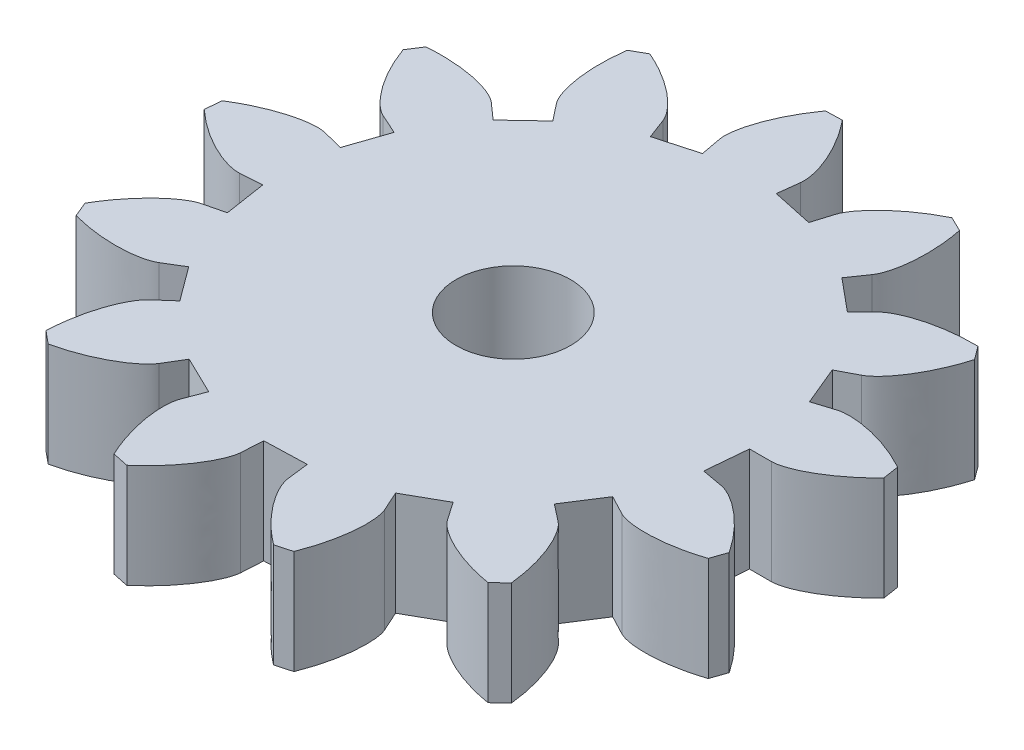
SolidWorks part; units mm, degrees
ref_plane "Front Plane" through (0, 0, 0) normal (0, 0, 1) x (1, 0, 0)
ref_plane "Top Plane" through (0, 0, 0) normal (0, 1, 0) x (1, 0, 0)
ref_plane "Right Plane" through (0, 0, 0) normal (1, 0, 0) x (0, 0, -1)
sketch "Sketch1" plane through (0, 0, 0) normal (0, 1, 0) x (1, 0, 0)
  circle A0 centre (0, 0) radius 8.2743 construction
  circle A1 centre (0, 0) radius 8.2743
sketch "Sketch2" plane through (0, 0, 0) normal (0, 1, 0) x (1, 0, 0)
  line L0 (6.8098, 0) -> (7.4374, 0)
  line L1 (7.4374, 0) -> (7.4435, 0.0002)
  line L2 (7.4435, 0.0002) -> (7.455, 0.0009)
  line L3 (7.455, 0.0009) -> (7.4719, 0.0023)
  line L4 (7.4719, 0.0023) -> (7.494, 0.0048)
  line L5 (7.494, 0.0048) -> (7.5213, 0.0086)
  line L6 (7.5213, 0.0086) -> (7.5538, 0.0141)
  line L7 (7.5538, 0.0141) -> (7.5915, 0.0214)
  line L8 (7.5915, 0.0214) -> (7.6341, 0.0309)
  line L9 (7.6341, 0.0309) -> (7.6817, 0.0428)
  line L10 (7.6817, 0.0428) -> (7.7341, 0.0575)
  line L11 (7.7341, 0.0575) -> (7.7912, 0.0751)
  line L12 (7.7912, 0.0751) -> (7.8529, 0.096)
  line L13 (7.8529, 0.096) -> (7.9191, 0.1204)
  line L14 (7.9191, 0.1204) -> (7.9895, 0.1486)
  line L15 (7.9895, 0.1486) -> (8.0641, 0.1807)
  line L16 (8.0641, 0.1807) -> (8.1427, 0.2171)
  line L17 (8.1427, 0.2171) -> (8.225, 0.258)
  line L18 (8.225, 0.258) -> (8.311, 0.3036)
  line L19 (8.311, 0.3036) -> (8.4004, 0.3541)
  line L20 (8.4004, 0.3541) -> (8.493, 0.4097)
  line L21 (8.493, 0.4097) -> (8.5886, 0.4707)
  line L22 (8.5886, 0.4707) -> (8.6869, 0.5373)
  line L23 (8.6869, 0.5373) -> (8.7878, 0.6095)
  line L24 (8.7878, 0.6095) -> (8.891, 0.6877)
  line L25 (8.891, 0.6877) -> (8.9962, 0.772)
  line L26 (8.9962, 0.772) -> (9.1033, 0.8626)
  line L27 (9.1033, 0.8626) -> (9.2118, 0.9596)
  line L28 (9.2118, 0.9596) -> (9.3216, 1.0631)
  line L29 (9.3216, 1.0631) -> (9.4324, 1.1733)
  line L30 (9.4324, 1.1733) -> (9.4602, 1.2019)
  line L31 (9.4602, 1.2019) -> (9.4672, 1.2092)
  line L32 (9.4672, 1.2092) -> (9.4689, 1.211)
  line L33 (9.4689, 1.211) -> (9.4692, 1.2112)
  line L34 (9.4692, 1.2112) -> (9.4693, 1.2114)
  line L35 (9.4693, 1.2114) -> (9.3971, 1.6821)
  line L36 (9.3971, 1.6821) -> (9.3969, 1.6823)
  line L37 (9.3969, 1.6823) -> (9.3966, 1.6825)
  line L38 (9.3966, 1.6825) -> (9.3944, 1.6837)
  line L39 (9.3944, 1.6837) -> (9.3856, 1.6885)
  line L40 (9.3856, 1.6885) -> (9.3505, 1.7074)
  line L41 (9.3505, 1.7074) -> (9.2118, 1.7794)
  line L42 (9.2118, 1.7794) -> (9.076, 1.8452)
  line L43 (9.076, 1.8452) -> (8.9434, 1.9052)
  line L44 (8.9434, 1.9052) -> (8.8141, 1.9595)
  line L45 (8.8141, 1.9595) -> (8.6884, 2.0084)
  line L46 (8.6884, 2.0084) -> (8.5666, 2.0521)
  line L47 (8.5666, 2.0521) -> (8.4487, 2.0908)
  line L48 (8.4487, 2.0908) -> (8.3349, 2.1248)
  line L49 (8.3349, 2.1248) -> (8.2254, 2.1544)
  line L50 (8.2254, 2.1544) -> (8.1204, 2.1797)
  line L51 (8.1204, 2.1797) -> (8.02, 2.2011)
  line L52 (8.02, 2.2011) -> (7.9243, 2.2189)
  line L53 (7.9243, 2.2189) -> (7.8335, 2.2332)
  line L54 (7.8335, 2.2332) -> (7.7476, 2.2443)
  line L55 (7.7476, 2.2443) -> (7.6668, 2.2527)
  line L56 (7.6668, 2.2527) -> (7.5912, 2.2584)
  line L57 (7.5912, 2.2584) -> (7.5207, 2.2618)
  line L58 (7.5207, 2.2618) -> (7.4556, 2.2633)
  line L59 (7.4556, 2.2633) -> (7.3958, 2.263)
  line L60 (7.3958, 2.263) -> (7.3415, 2.2613)
  line L61 (7.3415, 2.2613) -> (7.2925, 2.2584)
  line L62 (7.2925, 2.2584) -> (7.2489, 2.2547)
  line L63 (7.2489, 2.2547) -> (7.2109, 2.2504)
  line L64 (7.2109, 2.2504) -> (7.1782, 2.2458)
  line L65 (7.1782, 2.2458) -> (7.151, 2.2413)
  line L66 (7.151, 2.2413) -> (7.1291, 2.237)
  line L67 (7.1291, 2.237) -> (7.1126, 2.2334)
  line L68 (7.1126, 2.2334) -> (7.1015, 2.2306)
  line L69 (7.1015, 2.2306) -> (7.0955, 2.2289)
  line L70 (7.0955, 2.2289) -> (6.4968, 2.0408)
  line L71 (6.4968, 2.0408) -> (6.0298, 3.1647)
  line L72 (6.0298, 3.1647) -> (6.5855, 3.4563)
  line L73 (6.5855, 3.4563) -> (6.5908, 3.4594)
  line L74 (6.5908, 3.4594) -> (6.6007, 3.4653)
  line L75 (6.6007, 3.4653) -> (6.6149, 3.4744)
  line L76 (6.6149, 3.4744) -> (6.6333, 3.4869)
  line L77 (6.6333, 3.4869) -> (6.6558, 3.503)
  line L78 (6.6558, 3.503) -> (6.6821, 3.5229)
  line L79 (6.6821, 3.5229) -> (6.712, 3.5469)
  line L80 (6.712, 3.5469) -> (6.7453, 3.5751)
  line L81 (6.7453, 3.5751) -> (6.7819, 3.6078)
  line L82 (6.7819, 3.6078) -> (6.8215, 3.6451)
  line L83 (6.8215, 3.6451) -> (6.8639, 3.6873)
  line L84 (6.8639, 3.6873) -> (6.9088, 3.7345)
  line L85 (6.9088, 3.7345) -> (6.956, 3.7868)
  line L86 (6.956, 3.7868) -> (7.0053, 3.8445)
  line L87 (7.0053, 3.8445) -> (7.0564, 3.9076)
  line L88 (7.0564, 3.9076) -> (7.1091, 3.9763)
  line L89 (7.1091, 3.9763) -> (7.163, 4.0508)
  line L90 (7.163, 4.0508) -> (7.218, 4.1311)
  line L91 (7.218, 4.1311) -> (7.2736, 4.2174)
  line L92 (7.2736, 4.2174) -> (7.3298, 4.3097)
  line L93 (7.3298, 4.3097) -> (7.3861, 4.4081)
  line L94 (7.3861, 4.4081) -> (7.4422, 4.5127)
  line L95 (7.4422, 4.5127) -> (7.498, 4.6236)
  line L96 (7.498, 4.6236) -> (7.553, 4.7408)
  line L97 (7.553, 4.7408) -> (7.607, 4.8644)
  line L98 (7.607, 4.8644) -> (7.6597, 4.9943)
  line L99 (7.6597, 4.9943) -> (7.7107, 5.1306)
  line L100 (7.7107, 5.1306) -> (7.7598, 5.2733)
  line L101 (7.7598, 5.2733) -> (7.8067, 5.4224)
  line L102 (7.8067, 5.4224) -> (7.8181, 5.4607)
  line L103 (7.8181, 5.4607) -> (7.8209, 5.4703)
  line L104 (7.8209, 5.4703) -> (7.8216, 5.4727)
  line L105 (7.8216, 5.4727) -> (7.8217, 5.473)
  line L106 (7.8217, 5.473) -> (7.8216, 5.4732)
  line L107 (7.8216, 5.4732) -> (7.539, 5.8565)
  line L108 (7.539, 5.8565) -> (7.5387, 5.8566)
  line L109 (7.5387, 5.8566) -> (7.5384, 5.8566)
  line L110 (7.5384, 5.8566) -> (7.5359, 5.8566)
  line L111 (7.5359, 5.8566) -> (7.5259, 5.8568)
  line L112 (7.5259, 5.8568) -> (7.486, 5.8572)
  line L113 (7.486, 5.8572) -> (7.3297, 5.8565)
  line L114 (7.3297, 5.8565) -> (7.1789, 5.8517)
  line L115 (7.1789, 5.8517) -> (7.0336, 5.8432)
  line L116 (7.0336, 5.8432) -> (6.8939, 5.8312)
  line L117 (6.8939, 5.8312) -> (6.7599, 5.8161)
  line L118 (6.7599, 5.8161) -> (6.6317, 5.7981)
  line L119 (6.6317, 5.7981) -> (6.5093, 5.7776)
  line L120 (6.5093, 5.7776) -> (6.3927, 5.7549)
  line L121 (6.3927, 5.7549) -> (6.282, 5.7302)
  line L122 (6.282, 5.7302) -> (6.1773, 5.7038)
  line L123 (6.1773, 5.7038) -> (6.0784, 5.6761)
  line L124 (6.0784, 5.6761) -> (5.9855, 5.6473)
  line L125 (5.9855, 5.6473) -> (5.8984, 5.6178)
  line L126 (5.8984, 5.6178) -> (5.8172, 5.5878)
  line L127 (5.8172, 5.5878) -> (5.7418, 5.5576)
  line L128 (5.7418, 5.5576) -> (5.6721, 5.5275)
  line L129 (5.6721, 5.5275) -> (5.6082, 5.4978)
  line L130 (5.6082, 5.4978) -> (5.5498, 5.4688)
  line L131 (5.5498, 5.4688) -> (5.497, 5.4408)
  line L132 (5.497, 5.4408) -> (5.4497, 5.414)
  line L133 (5.4497, 5.414) -> (5.4076, 5.3887)
  line L134 (5.4076, 5.3887) -> (5.3708, 5.3652)
  line L135 (5.3708, 5.3652) -> (5.3391, 5.3437)
  line L136 (5.3391, 5.3437) -> (5.3123, 5.3245)
  line L137 (5.3123, 5.3245) -> (5.2903, 5.3078)
  line L138 (5.2903, 5.3078) -> (5.2729, 5.2939)
  line L139 (5.2729, 5.2939) -> (5.26, 5.283)
  line L140 (5.26, 5.283) -> (5.2514, 5.2753)
  line L141 (5.2514, 5.2753) -> (5.247, 5.2711)
  line L142 (5.247, 5.2711) -> (4.8042, 4.8263)
  line L143 (4.8042, 4.8263) -> (3.8684, 5.6043)
  line L144 (3.8684, 5.6043) -> (4.2249, 6.1208)
  line L145 (4.2249, 6.1208) -> (4.2282, 6.126)
  line L146 (4.2282, 6.126) -> (4.2342, 6.1359)
  line L147 (4.2342, 6.1359) -> (4.2426, 6.1505)
  line L148 (4.2426, 6.1505) -> (4.2531, 6.1702)
  line L149 (4.2531, 6.1702) -> (4.2655, 6.1948)
  line L150 (4.2655, 6.1948) -> (4.2795, 6.2247)
  line L151 (4.2795, 6.2247) -> (4.2948, 6.2598)
  line L152 (4.2948, 6.2598) -> (4.3112, 6.3003)
  line L153 (4.3112, 6.3003) -> (4.3284, 6.3462)
  line L154 (4.3284, 6.3462) -> (4.3462, 6.3977)
  line L155 (4.3462, 6.3977) -> (4.3641, 6.4547)
  line L156 (4.3641, 6.4547) -> (4.3819, 6.5174)
  line L157 (4.3819, 6.5174) -> (4.3994, 6.5857)
  line L158 (4.3994, 6.5857) -> (4.4163, 6.6596)
  line L159 (4.4163, 6.6596) -> (4.4322, 6.7393)
  line L160 (4.4322, 6.7393) -> (4.4469, 6.8246)
  line L161 (4.4469, 6.8246) -> (4.46, 6.9156)
  line L162 (4.46, 6.9156) -> (4.4714, 7.0123)
  line L163 (4.4714, 7.0123) -> (4.4806, 7.1145)
  line L164 (4.4806, 7.1145) -> (4.4874, 7.2223)
  line L165 (4.4874, 7.2223) -> (4.4915, 7.3356)
  line L166 (4.4915, 7.3356) -> (4.4926, 7.4544)
  line L167 (4.4926, 7.4544) -> (4.4904, 7.5785)
  line L168 (4.4904, 7.5785) -> (4.4847, 7.7078)
  line L169 (4.4847, 7.7078) -> (4.4751, 7.8423)
  line L170 (4.4751, 7.8423) -> (4.4613, 7.9819)
  line L171 (4.4613, 7.9819) -> (4.4432, 8.1263)
  line L172 (4.4432, 8.1263) -> (4.4204, 8.2755)
  line L173 (4.4204, 8.2755) -> (4.3926, 8.4293)
  line L174 (4.3926, 8.4293) -> (4.3849, 8.4684)
  line L175 (4.3849, 8.4684) -> (4.3829, 8.4782)
  line L176 (4.3829, 8.4782) -> (4.3824, 8.4807)
  line L177 (4.3824, 8.4807) -> (4.3823, 8.481)
  line L178 (4.3823, 8.481) -> (4.3822, 8.4812)
  line L179 (4.3822, 8.4812) -> (3.9538, 8.6892)
  line L180 (3.9538, 8.6892) -> (3.9535, 8.6892)
  line L181 (3.9535, 8.6892) -> (3.9533, 8.689)
  line L182 (3.9533, 8.689) -> (3.951, 8.6879)
  line L183 (3.951, 8.6879) -> (3.9421, 8.6834)
  line L184 (3.9421, 8.6834) -> (3.9065, 8.6652)
  line L185 (3.9065, 8.6652) -> (3.7685, 8.5919)
  line L186 (3.7685, 8.5919) -> (3.6371, 8.5176)
  line L187 (3.6371, 8.5176) -> (3.5125, 8.4425)
  line L188 (3.5125, 8.4425) -> (3.3943, 8.367)
  line L189 (3.3943, 8.367) -> (3.2827, 8.2914)
  line L190 (3.2827, 8.2914) -> (3.1775, 8.2159)
  line L191 (3.1775, 8.2159) -> (3.0787, 8.1408)
  line L192 (3.0787, 8.1408) -> (2.986, 8.0665)
  line L193 (2.986, 8.0665) -> (2.8995, 7.9932)
  line L194 (2.8995, 7.9932) -> (2.819, 7.9212)
  line L195 (2.819, 7.9212) -> (2.7444, 7.8507)
  line L196 (2.7444, 7.8507) -> (2.6754, 7.782)
  line L197 (2.6754, 7.782) -> (2.6121, 7.7154)
  line L198 (2.6121, 7.7154) -> (2.5541, 7.6511)
  line L199 (2.5541, 7.6511) -> (2.5013, 7.5893)
  line L200 (2.5013, 7.5893) -> (2.4537, 7.5303)
  line L201 (2.4537, 7.5303) -> (2.4108, 7.4743)
  line L202 (2.4108, 7.4743) -> (2.3726, 7.4215)
  line L203 (2.3726, 7.4215) -> (2.3389, 7.3722)
  line L204 (2.3389, 7.3722) -> (2.3094, 7.3265)
  line L205 (2.3094, 7.3265) -> (2.284, 7.2845)
  line L206 (2.284, 7.2845) -> (2.2623, 7.2466)
  line L207 (2.2623, 7.2466) -> (2.2442, 7.2128)
  line L208 (2.2442, 7.2128) -> (2.2294, 7.1833)
  line L209 (2.2294, 7.1833) -> (2.2177, 7.1583)
  line L210 (2.2177, 7.1583) -> (2.2088, 7.1379)
  line L211 (2.2088, 7.1379) -> (2.2024, 7.1223)
  line L212 (2.2024, 7.1223) -> (2.1984, 7.1115)
  line L213 (2.1984, 7.1115) -> (2.1964, 7.1057)
  line L214 (2.1964, 7.1057) -> (2.011, 6.5061)
  line L215 (2.011, 6.5061) -> (0.8208, 6.7601)
  line L216 (0.8208, 6.7601) -> (0.8965, 7.3831)
  line L217 (0.8965, 7.3831) -> (0.897, 7.3893)
  line L218 (0.897, 7.3893) -> (0.8977, 7.4008)
  line L219 (0.8977, 7.4008) -> (0.8983, 7.4177)
  line L220 (0.8983, 7.4177) -> (0.8985, 7.4399)
  line L221 (0.8985, 7.4399) -> (0.898, 7.4675)
  line L222 (0.898, 7.4675) -> (0.8965, 7.5005)
  line L223 (0.8965, 7.5005) -> (0.8938, 7.5387)
  line L224 (0.8938, 7.5387) -> (0.8895, 7.5822)
  line L225 (0.8895, 7.5822) -> (0.8834, 7.6309)
  line L226 (0.8834, 7.6309) -> (0.8752, 7.6846)
  line L227 (0.8752, 7.6846) -> (0.8645, 7.7435)
  line L228 (0.8645, 7.7435) -> (0.8512, 7.8072)
  line L229 (0.8512, 7.8072) -> (0.835, 7.8758)
  line L230 (0.835, 7.8758) -> (0.8156, 7.9492)
  line L231 (0.8156, 7.9492) -> (0.7926, 8.0271)
  line L232 (0.7926, 8.0271) -> (0.766, 8.1095)
  line L233 (0.766, 8.1095) -> (0.7353, 8.1962)
  line L234 (0.7353, 8.1962) -> (0.7004, 8.287)
  line L235 (0.7004, 8.287) -> (0.6611, 8.3818)
  line L236 (0.6611, 8.3818) -> (0.617, 8.4804)
  line L237 (0.617, 8.4804) -> (0.568, 8.5827)
  line L238 (0.568, 8.5827) -> (0.5138, 8.6883)
  line L239 (0.5138, 8.6883) -> (0.4542, 8.7972)
  line L240 (0.4542, 8.7972) -> (0.389, 8.9091)
  line L241 (0.389, 8.9091) -> (0.318, 9.0237)
  line L242 (0.318, 9.0237) -> (0.241, 9.1409)
  line L243 (0.241, 9.1409) -> (0.1578, 9.2603)
  line L244 (0.1578, 9.2603) -> (0.0682, 9.3818)
  line L245 (0.0682, 9.3818) -> (-0.0278, 9.5051)
  line L246 (-0.0278, 9.5051) -> (-0.0529, 9.5361)
  line L247 (-0.0529, 9.5361) -> (-0.0592, 9.5439)
  line L248 (-0.0592, 9.5439) -> (-0.0608, 9.5459)
  line L249 (-0.0608, 9.5459) -> (-0.061, 9.5461)
  line L250 (-0.061, 9.5461) -> (-0.0612, 9.5462)
  line L251 (-0.0612, 9.5462) -> (-0.5372, 9.5313)
  line L252 (-0.5372, 9.5313) -> (-0.5374, 9.5312)
  line L253 (-0.5374, 9.5312) -> (-0.5375, 9.5309)
  line L254 (-0.5375, 9.5309) -> (-0.539, 9.5289)
  line L255 (-0.539, 9.5289) -> (-0.5448, 9.5207)
  line L256 (-0.5448, 9.5207) -> (-0.5679, 9.4881)
  line L257 (-0.5679, 9.4881) -> (-0.656, 9.3591)
  line L258 (-0.656, 9.3591) -> (-0.7378, 9.2322)
  line L259 (-0.7378, 9.2322) -> (-0.8133, 9.1078)
  line L260 (-0.8133, 9.1078) -> (-0.8828, 8.986)
  line L261 (-0.8828, 8.986) -> (-0.9465, 8.8672)
  line L262 (-0.9465, 8.8672) -> (-1.0046, 8.7515)
  line L263 (-1.0046, 8.7515) -> (-1.0572, 8.6391)
  line L264 (-1.0572, 8.6391) -> (-1.1047, 8.5302)
  line L265 (-1.1047, 8.5302) -> (-1.1472, 8.4251)
  line L266 (-1.1472, 8.4251) -> (-1.185, 8.3239)
  line L267 (-1.185, 8.3239) -> (-1.2184, 8.2268)
  line L268 (-1.2184, 8.2268) -> (-1.2475, 8.134)
  line L269 (-1.2475, 8.134) -> (-1.2727, 8.0455)
  line L270 (-1.2727, 8.0455) -> (-1.2941, 7.9616)
  line L271 (-1.2941, 7.9616) -> (-1.3121, 7.8824)
  line L272 (-1.3121, 7.8824) -> (-1.3269, 7.808)
  line L273 (-1.3269, 7.808) -> (-1.3388, 7.7385)
  line L274 (-1.3388, 7.7385) -> (-1.3481, 7.6741)
  line L275 (-1.3481, 7.6741) -> (-1.355, 7.6147)
  line L276 (-1.355, 7.6147) -> (-1.3599, 7.5605)
  line L277 (-1.3599, 7.5605) -> (-1.3629, 7.5115)
  line L278 (-1.3629, 7.5115) -> (-1.3645, 7.4679)
  line L279 (-1.3645, 7.4679) -> (-1.3648, 7.4295)
  line L280 (-1.3648, 7.4295) -> (-1.3642, 7.3966)
  line L281 (-1.3642, 7.3966) -> (-1.363, 7.369)
  line L282 (-1.363, 7.369) -> (-1.3614, 7.3468)
  line L283 (-1.3614, 7.3468) -> (-1.3597, 7.33)
  line L284 (-1.3597, 7.33) -> (-1.3583, 7.3186)
  line L285 (-1.3583, 7.3186) -> (-1.3574, 7.3125)
  line L286 (-1.3574, 7.3125) -> (-1.2429, 6.6954)
  line L287 (-1.2429, 6.6954) -> (-2.4148, 6.3673)
  line L288 (-2.4148, 6.3673) -> (-2.6373, 6.9541)
  line L289 (-2.6373, 6.9541) -> (-2.6397, 6.9598)
  line L290 (-2.6397, 6.9598) -> (-2.6444, 6.9703)
  line L291 (-2.6444, 6.9703) -> (-2.6517, 6.9855)
  line L292 (-2.6517, 6.9855) -> (-2.6619, 7.0053)
  line L293 (-2.6619, 7.0053) -> (-2.6752, 7.0295)
  line L294 (-2.6752, 7.0295) -> (-2.6918, 7.058)
  line L295 (-2.6918, 7.058) -> (-2.712, 7.0906)
  line L296 (-2.712, 7.0906) -> (-2.736, 7.1271)
  line L297 (-2.736, 7.1271) -> (-2.764, 7.1673)
  line L298 (-2.764, 7.1673) -> (-2.7963, 7.2111)
  line L299 (-2.7963, 7.2111) -> (-2.8331, 7.2583)
  line L300 (-2.8331, 7.2583) -> (-2.8745, 7.3086)
  line L301 (-2.8745, 7.3086) -> (-2.9207, 7.3618)
  line L302 (-2.9207, 7.3618) -> (-2.972, 7.4176)
  line L303 (-2.972, 7.4176) -> (-3.0285, 7.476)
  line L304 (-3.0285, 7.476) -> (-3.0904, 7.5365)
  line L305 (-3.0904, 7.5365) -> (-3.1578, 7.5991)
  line L306 (-3.1578, 7.5991) -> (-3.2309, 7.6633)
  line L307 (-3.2309, 7.6633) -> (-3.3099, 7.729)
  line L308 (-3.3099, 7.729) -> (-3.3947, 7.7958)
  line L309 (-3.3947, 7.7958) -> (-3.4857, 7.8635)
  line L310 (-3.4857, 7.8635) -> (-3.5828, 7.9319)
  line L311 (-3.5828, 7.9319) -> (-3.6861, 8.0006)
  line L312 (-3.6861, 8.0006) -> (-3.7958, 8.0694)
  line L313 (-3.7958, 8.0694) -> (-3.912, 8.1379)
  line L314 (-3.912, 8.1379) -> (-4.0346, 8.2058)
  line L315 (-4.0346, 8.2058) -> (-4.1638, 8.2729)
  line L316 (-4.1638, 8.2729) -> (-4.2995, 8.3389)
  line L317 (-4.2995, 8.3389) -> (-4.4419, 8.4034)
  line L318 (-4.4419, 8.4034) -> (-4.4785, 8.4193)
  line L319 (-4.4785, 8.4193) -> (-4.4877, 8.4232)
  line L320 (-4.4877, 8.4232) -> (-4.49, 8.4242)
  line L321 (-4.49, 8.4242) -> (-4.4903, 8.4243)
  line L322 (-4.4903, 8.4243) -> (-4.4905, 8.4243)
  line L323 (-4.4905, 8.4243) -> (-4.9051, 8.1899)
  line L324 (-4.9051, 8.1899) -> (-4.9052, 8.1897)
  line L325 (-4.9052, 8.1897) -> (-4.9052, 8.1894)
  line L326 (-4.9052, 8.1894) -> (-4.9056, 8.1869)
  line L327 (-4.9056, 8.1869) -> (-4.9069, 8.177)
  line L328 (-4.9069, 8.177) -> (-4.9122, 8.1374)
  line L329 (-4.9122, 8.1374) -> (-4.9303, 7.9822)
  line L330 (-4.9303, 7.9822) -> (-4.9437, 7.8319)
  line L331 (-4.9437, 7.8319) -> (-4.9528, 7.6866)
  line L332 (-4.9528, 7.6866) -> (-4.9577, 7.5465)
  line L333 (-4.9577, 7.5465) -> (-4.9589, 7.4116)
  line L334 (-4.9589, 7.4116) -> (-4.9565, 7.2822)
  line L335 (-4.9565, 7.2822) -> (-4.9509, 7.1582)
  line L336 (-4.9509, 7.1582) -> (-4.9424, 7.0398)
  line L337 (-4.9424, 7.0398) -> (-4.9312, 6.9269)
  line L338 (-4.9312, 6.9269) -> (-4.9176, 6.8197)
  line L339 (-4.9176, 6.8197) -> (-4.902, 6.7183)
  line L340 (-4.902, 6.7183) -> (-4.8847, 6.6225)
  line L341 (-4.8847, 6.6225) -> (-4.8658, 6.5325)
  line L342 (-4.8658, 6.5325) -> (-4.8458, 6.4483)
  line L343 (-4.8458, 6.4483) -> (-4.825, 6.3698)
  line L344 (-4.825, 6.3698) -> (-4.8035, 6.297)
  line L345 (-4.8035, 6.297) -> (-4.7818, 6.23)
  line L346 (-4.7818, 6.23) -> (-4.76, 6.1686)
  line L347 (-4.76, 6.1686) -> (-4.7385, 6.1128)
  line L348 (-4.7385, 6.1128) -> (-4.7176, 6.0625)
  line L349 (-4.7176, 6.0625) -> (-4.6976, 6.0177)
  line L350 (-4.6976, 6.0177) -> (-4.6787, 5.9784)
  line L351 (-4.6787, 5.9784) -> (-4.6612, 5.9443)
  line L352 (-4.6612, 5.9443) -> (-4.6453, 5.9154)
  line L353 (-4.6453, 5.9154) -> (-4.6314, 5.8915)
  line L354 (-4.6314, 5.8915) -> (-4.6197, 5.8726)
  line L355 (-4.6197, 5.8726) -> (-4.6104, 5.8585)
  line L356 (-4.6104, 5.8585) -> (-4.6038, 5.849)
  line L357 (-4.6038, 5.849) -> (-4.6002, 5.8441)
  line L358 (-4.6002, 5.8441) -> (-4.212, 5.3509)
  line L359 (-4.212, 5.3509) -> (-5.0972, 4.5157)
  line L360 (-5.0972, 4.5157) -> (-5.567, 4.9319)
  line L361 (-5.567, 4.9319) -> (-5.5717, 4.9358)
  line L362 (-5.5717, 4.9358) -> (-5.5808, 4.9429)
  line L363 (-5.5808, 4.9429) -> (-5.5943, 4.953)
  line L364 (-5.5943, 4.953) -> (-5.6125, 4.9658)
  line L365 (-5.6125, 4.9658) -> (-5.6355, 4.9811)
  line L366 (-5.6355, 4.9811) -> (-5.6635, 4.9986)
  line L367 (-5.6635, 4.9986) -> (-5.6965, 5.0181)
  line L368 (-5.6965, 5.0181) -> (-5.7347, 5.0392)
  line L369 (-5.7347, 5.0392) -> (-5.7782, 5.0618)
  line L370 (-5.7782, 5.0618) -> (-5.8272, 5.0856)
  line L371 (-5.8272, 5.0856) -> (-5.8816, 5.1103)
  line L372 (-5.8816, 5.1103) -> (-5.9417, 5.1356)
  line L373 (-5.9417, 5.1356) -> (-6.0074, 5.1612)
  line L374 (-6.0074, 5.1612) -> (-6.0787, 5.1868)
  line L375 (-6.0787, 5.1868) -> (-6.1559, 5.2122)
  line L376 (-6.1559, 5.2122) -> (-6.2388, 5.2371)
  line L377 (-6.2388, 5.2371) -> (-6.3276, 5.2611)
  line L378 (-6.3276, 5.2611) -> (-6.4222, 5.284)
  line L379 (-6.4222, 5.284) -> (-6.5226, 5.3055)
  line L380 (-6.5226, 5.3055) -> (-6.6288, 5.3252)
  line L381 (-6.6288, 5.3252) -> (-6.7408, 5.3429)
  line L382 (-6.7408, 5.3429) -> (-6.8585, 5.3584)
  line L383 (-6.8585, 5.3584) -> (-6.982, 5.3712)
  line L384 (-6.982, 5.3712) -> (-7.1111, 5.381)
  line L385 (-7.1111, 5.381) -> (-7.2457, 5.3877)
  line L386 (-7.2457, 5.3877) -> (-7.3859, 5.3909)
  line L387 (-7.3859, 5.3909) -> (-7.5315, 5.3903)
  line L388 (-7.5315, 5.3903) -> (-7.6823, 5.3856)
  line L389 (-7.6823, 5.3856) -> (-7.8383, 5.3766)
  line L390 (-7.8383, 5.3766) -> (-7.8781, 5.3736)
  line L391 (-7.8781, 5.3736) -> (-7.8881, 5.3729)
  line L392 (-7.8881, 5.3729) -> (-7.8906, 5.3727)
  line L393 (-7.8906, 5.3727) -> (-7.8909, 5.3726)
  line L394 (-7.8909, 5.3726) -> (-7.8912, 5.3725)
  line L395 (-7.8912, 5.3725) -> (-8.1493, 4.9723)
  line L396 (-8.1493, 4.9723) -> (-8.1493, 4.9721)
  line L397 (-8.1493, 4.9721) -> (-8.1492, 4.9718)
  line L398 (-8.1492, 4.9718) -> (-8.1483, 4.9694)
  line L399 (-8.1483, 4.9694) -> (-8.1449, 4.96)
  line L400 (-8.1449, 4.96) -> (-8.1312, 4.9225)
  line L401 (-8.1312, 4.9225) -> (-8.0751, 4.7767)
  line L402 (-8.0751, 4.7767) -> (-8.0171, 4.6373)
  line L403 (-8.0171, 4.6373) -> (-7.9576, 4.5045)
  line L404 (-7.9576, 4.5045) -> (-7.8969, 4.3781)
  line L405 (-7.8969, 4.3781) -> (-7.8352, 4.2582)
  line L406 (-7.8352, 4.2582) -> (-7.773, 4.1447)
  line L407 (-7.773, 4.1447) -> (-7.7104, 4.0375)
  line L408 (-7.7104, 4.0375) -> (-7.6478, 3.9366)
  line L409 (-7.6478, 3.9366) -> (-7.5854, 3.8419)
  line L410 (-7.5854, 3.8419) -> (-7.5236, 3.7533)
  line L411 (-7.5236, 3.7533) -> (-7.4627, 3.6707)
  line L412 (-7.4627, 3.6707) -> (-7.4028, 3.5939)
  line L413 (-7.4028, 3.5939) -> (-7.3443, 3.523)
  line L414 (-7.3443, 3.523) -> (-7.2874, 3.4577)
  line L415 (-7.2874, 3.4577) -> (-7.2325, 3.3979)
  line L416 (-7.2325, 3.3979) -> (-7.1797, 3.3434)
  line L417 (-7.1797, 3.3434) -> (-7.1292, 3.2942)
  line L418 (-7.1292, 3.2942) -> (-7.0814, 3.2499)
  line L419 (-7.0814, 3.2499) -> (-7.0365, 3.2105)
  line L420 (-7.0365, 3.2105) -> (-6.9947, 3.1757)
  line L421 (-6.9947, 3.1757) -> (-6.9561, 3.1454)
  line L422 (-6.9561, 3.1454) -> (-6.9211, 3.1193)
  line L423 (-6.9211, 3.1193) -> (-6.8897, 3.0972)
  line L424 (-6.8897, 3.0972) -> (-6.8622, 3.079)
  line L425 (-6.8622, 3.079) -> (-6.8388, 3.0643)
  line L426 (-6.8388, 3.0643) -> (-6.8197, 3.0531)
  line L427 (-6.8197, 3.0531) -> (-6.8049, 3.0449)
  line L428 (-6.8049, 3.0449) -> (-6.7947, 3.0395)
  line L429 (-6.7947, 3.0395) -> (-6.7891, 3.0368)
  line L430 (-6.7891, 3.0368) -> (-6.2162, 2.7806)
  line L431 (-6.2162, 2.7806) -> (-6.6119, 1.6297)
  line L432 (-6.6119, 1.6297) -> (-7.2213, 1.7799)
  line L433 (-7.2213, 1.7799) -> (-7.2273, 1.7811)
  line L434 (-7.2273, 1.7811) -> (-7.2386, 1.7832)
  line L435 (-7.2386, 1.7832) -> (-7.2553, 1.7859)
  line L436 (-7.2553, 1.7859) -> (-7.2774, 1.7887)
  line L437 (-7.2774, 1.7887) -> (-7.3048, 1.7916)
  line L438 (-7.3048, 1.7916) -> (-7.3377, 1.7941)
  line L439 (-7.3377, 1.7941) -> (-7.376, 1.796)
  line L440 (-7.376, 1.796) -> (-7.4197, 1.797)
  line L441 (-7.4197, 1.797) -> (-7.4687, 1.7968)
  line L442 (-7.4687, 1.7968) -> (-7.5231, 1.7951)
  line L443 (-7.5231, 1.7951) -> (-7.5828, 1.7916)
  line L444 (-7.5828, 1.7916) -> (-7.6477, 1.7861)
  line L445 (-7.6477, 1.7861) -> (-7.7178, 1.7782)
  line L446 (-7.7178, 1.7782) -> (-7.7929, 1.7678)
  line L447 (-7.7929, 1.7678) -> (-7.873, 1.7544)
  line L448 (-7.873, 1.7544) -> (-7.958, 1.7379)
  line L449 (-7.958, 1.7379) -> (-8.0478, 1.7179)
  line L450 (-8.0478, 1.7179) -> (-8.1421, 1.6942)
  line L451 (-8.1421, 1.6942) -> (-8.241, 1.6666)
  line L452 (-8.241, 1.6666) -> (-8.3442, 1.6347)
  line L453 (-8.3442, 1.6347) -> (-8.4517, 1.5984)
  line L454 (-8.4517, 1.5984) -> (-8.5631, 1.5573)
  line L455 (-8.5631, 1.5573) -> (-8.6783, 1.5112)
  line L456 (-8.6783, 1.5112) -> (-8.7972, 1.46)
  line L457 (-8.7972, 1.46) -> (-8.9196, 1.4033)
  line L458 (-8.9196, 1.4033) -> (-9.0452, 1.341)
  line L459 (-9.0452, 1.341) -> (-9.1738, 1.2728)
  line L460 (-9.1738, 1.2728) -> (-9.3052, 1.1986)
  line L461 (-9.3052, 1.1986) -> (-9.4391, 1.1181)
  line L462 (-9.4391, 1.1181) -> (-9.473, 1.097)
  line L463 (-9.473, 1.097) -> (-9.4815, 1.0916)
  line L464 (-9.4815, 1.0916) -> (-9.4836, 1.0903)
  line L465 (-9.4836, 1.0903) -> (-9.4839, 1.0901)
  line L466 (-9.4839, 1.0901) -> (-9.484, 1.0899)
  line L467 (-9.484, 1.0899) -> (-9.5266, 0.6156)
  line L468 (-9.5266, 0.6156) -> (-9.5265, 0.6154)
  line L469 (-9.5265, 0.6154) -> (-9.5262, 0.6152)
  line L470 (-9.5262, 0.6152) -> (-9.5244, 0.6135)
  line L471 (-9.5244, 0.6135) -> (-9.517, 0.6067)
  line L472 (-9.517, 0.6067) -> (-9.4874, 0.5799)
  line L473 (-9.4874, 0.5799) -> (-9.3699, 0.4769)
  line L474 (-9.3699, 0.4769) -> (-9.2538, 0.3804)
  line L475 (-9.2538, 0.3804) -> (-9.1394, 0.2904)
  line L476 (-9.1394, 0.2904) -> (-9.0269, 0.2068)
  line L477 (-9.0269, 0.2068) -> (-8.9166, 0.1292)
  line L478 (-8.9166, 0.1292) -> (-8.8087, 0.0576)
  line L479 (-8.8087, 0.0576) -> (-8.7035, -0.0082)
  line L480 (-8.7035, -0.0082) -> (-8.6012, -0.0684)
  line L481 (-8.6012, -0.0684) -> (-8.502, -0.1233)
  line L482 (-8.502, -0.1233) -> (-8.4061, -0.1731)
  line L483 (-8.4061, -0.1731) -> (-8.3137, -0.2179)
  line L484 (-8.3137, -0.2179) -> (-8.225, -0.258)
  line L485 (-8.225, -0.258) -> (-8.1403, -0.2936)
  line L486 (-8.1403, -0.2936) -> (-8.0596, -0.325)
  line L487 (-8.0596, -0.325) -> (-7.9831, -0.3524)
  line L488 (-7.9831, -0.3524) -> (-7.911, -0.3761)
  line L489 (-7.911, -0.3761) -> (-7.8435, -0.3963)
  line L490 (-7.8435, -0.3963) -> (-7.7806, -0.4133)
  line L491 (-7.7806, -0.4133) -> (-7.7225, -0.4273)
  line L492 (-7.7225, -0.4273) -> (-7.6693, -0.4386)
  line L493 (-7.6693, -0.4386) -> (-7.6211, -0.4476)
  line L494 (-7.6211, -0.4476) -> (-7.5779, -0.4544)
  line L495 (-7.5779, -0.4544) -> (-7.5399, -0.4593)
  line L496 (-7.5399, -0.4593) -> (-7.5071, -0.4627)
  line L497 (-7.5071, -0.4627) -> (-7.4795, -0.4648)
  line L498 (-7.4795, -0.4648) -> (-7.4573, -0.4659)
  line L499 (-7.4573, -0.4659) -> (-7.4404, -0.4663)
  line L500 (-7.4404, -0.4663) -> (-7.4289, -0.4662)
  line L501 (-7.4289, -0.4662) -> (-7.4228, -0.4661)
  line L502 (-7.4228, -0.4661) -> (-6.7964, -0.4267)
  line L503 (-6.7964, -0.4267) -> (-6.6119, -1.6297)
  line L504 (-6.6119, -1.6297) -> (-7.2213, -1.7799)
  line L505 (-7.2213, -1.7799) -> (-7.2272, -1.7816)
  line L506 (-7.2272, -1.7816) -> (-7.2382, -1.785)
  line L507 (-7.2382, -1.785) -> (-7.2542, -1.7904)
  line L508 (-7.2542, -1.7904) -> (-7.2751, -1.7981)
  line L509 (-7.2751, -1.7981) -> (-7.3007, -1.8084)
  line L510 (-7.3007, -1.8084) -> (-7.331, -1.8214)
  line L511 (-7.331, -1.8214) -> (-7.3658, -1.8375)
  line L512 (-7.3658, -1.8375) -> (-7.4049, -1.857)
  line L513 (-7.4049, -1.857) -> (-7.4482, -1.8799)
  line L514 (-7.4482, -1.8799) -> (-7.4956, -1.9067)
  line L515 (-7.4956, -1.9067) -> (-7.5468, -1.9375)
  line L516 (-7.5468, -1.9375) -> (-7.6017, -1.9726)
  line L517 (-7.6017, -1.9726) -> (-7.6601, -2.0121)
  line L518 (-7.6601, -2.0121) -> (-7.7218, -2.0563)
  line L519 (-7.7218, -2.0563) -> (-7.7865, -2.1053)
  line L520 (-7.7865, -2.1053) -> (-7.8541, -2.1595)
  line L521 (-7.8541, -2.1595) -> (-7.9243, -2.2189)
  line L522 (-7.9243, -2.2189) -> (-7.9969, -2.2837)
  line L523 (-7.9969, -2.2837) -> (-8.0716, -2.3541)
  line L524 (-8.0716, -2.3541) -> (-8.1481, -2.4303)
  line L525 (-8.1481, -2.4303) -> (-8.2264, -2.5124)
  line L526 (-8.2264, -2.5124) -> (-8.3059, -2.6006)
  line L527 (-8.3059, -2.6006) -> (-8.3866, -2.6949)
  line L528 (-8.3866, -2.6949) -> (-8.4681, -2.7955)
  line L529 (-8.4681, -2.7955) -> (-8.5501, -2.9026)
  line L530 (-8.5501, -2.9026) -> (-8.6323, -3.0161)
  line L531 (-8.6323, -3.0161) -> (-8.7145, -3.1362)
  line L532 (-8.7145, -3.1362) -> (-8.7963, -3.263)
  line L533 (-8.7963, -3.263) -> (-8.8775, -3.3966)
  line L534 (-8.8775, -3.3966) -> (-8.8977, -3.431)
  line L535 (-8.8977, -3.431) -> (-8.9027, -3.4397)
  line L536 (-8.9027, -3.4397) -> (-8.904, -3.4418)
  line L537 (-8.904, -3.4418) -> (-8.9041, -3.4421)
  line L538 (-8.9041, -3.4421) -> (-8.9042, -3.4423)
  line L539 (-8.9042, -3.4423) -> (-8.7214, -3.8821)
  line L540 (-8.7214, -3.8821) -> (-8.7213, -3.8822)
  line L541 (-8.7213, -3.8822) -> (-8.7209, -3.8823)
  line L542 (-8.7209, -3.8823) -> (-8.7185, -3.883)
  line L543 (-8.7185, -3.883) -> (-8.7088, -3.8855)
  line L544 (-8.7088, -3.8855) -> (-8.6702, -3.8955)
  line L545 (-8.6702, -3.8955) -> (-8.5183, -3.9322)
  line L546 (-8.5183, -3.9322) -> (-8.3707, -3.9636)
  line L547 (-8.3707, -3.9636) -> (-8.2275, -3.9901)
  line L548 (-8.2275, -3.9901) -> (-8.089, -4.0119)
  line L549 (-8.089, -4.0119) -> (-7.9553, -4.0293)
  line L550 (-7.9553, -4.0293) -> (-7.8265, -4.0426)
  line L551 (-7.8265, -4.0426) -> (-7.7028, -4.052)
  line L552 (-7.7028, -4.052) -> (-7.5842, -4.0578)
  line L553 (-7.5842, -4.0578) -> (-7.4708, -4.0603)
  line L554 (-7.4708, -4.0603) -> (-7.3628, -4.0597)
  line L555 (-7.3628, -4.0597) -> (-7.2602, -4.0565)
  line L556 (-7.2602, -4.0565) -> (-7.163, -4.0508)
  line L557 (-7.163, -4.0508) -> (-7.0714, -4.0429)
  line L558 (-7.0714, -4.0429) -> (-6.9854, -4.0332)
  line L559 (-6.9854, -4.0332) -> (-6.9049, -4.022)
  line L560 (-6.9049, -4.022) -> (-6.8301, -4.0095)
  line L561 (-6.8301, -4.0095) -> (-6.7609, -3.9959)
  line L562 (-6.7609, -3.9959) -> (-6.6973, -3.9818)
  line L563 (-6.6973, -3.9818) -> (-6.6394, -3.9672)
  line L564 (-6.6394, -3.9672) -> (-6.587, -3.9525)
  line L565 (-6.587, -3.9525) -> (-6.5401, -3.938)
  line L566 (-6.5401, -3.938) -> (-6.4987, -3.924)
  line L567 (-6.4987, -3.924) -> (-6.4628, -3.9107)
  line L568 (-6.4628, -3.9107) -> (-6.4322, -3.8984)
  line L569 (-6.4322, -3.8984) -> (-6.4068, -3.8875)
  line L570 (-6.4068, -3.8875) -> (-6.3866, -3.8781)
  line L571 (-6.3866, -3.8781) -> (-6.3715, -3.8706)
  line L572 (-6.3715, -3.8706) -> (-6.3613, -3.8652)
  line L573 (-6.3613, -3.8652) -> (-6.3559, -3.8622)
  line L574 (-6.3559, -3.8622) -> (-5.8196, -3.5363)
  line L575 (-5.8196, -3.5363) -> (-5.0972, -4.5157)
  line L576 (-5.0972, -4.5157) -> (-5.5669, -4.9319)
  line L577 (-5.5669, -4.9319) -> (-5.5714, -4.9361)
  line L578 (-5.5714, -4.9361) -> (-5.5796, -4.9443)
  line L579 (-5.5796, -4.9443) -> (-5.5912, -4.9565)
  line L580 (-5.5912, -4.9565) -> (-5.6061, -4.973)
  line L581 (-5.6061, -4.973) -> (-5.6241, -4.994)
  line L582 (-5.6241, -4.994) -> (-5.6448, -5.0197)
  line L583 (-5.6448, -5.0197) -> (-5.6681, -5.0501)
  line L584 (-5.6681, -5.0501) -> (-5.6937, -5.0855)
  line L585 (-5.6937, -5.0855) -> (-5.7214, -5.126)
  line L586 (-5.7214, -5.126) -> (-5.7509, -5.1717)
  line L587 (-5.7509, -5.1717) -> (-5.782, -5.2228)
  line L588 (-5.782, -5.2228) -> (-5.8143, -5.2793)
  line L589 (-5.8143, -5.2793) -> (-5.8477, -5.3414)
  line L590 (-5.8477, -5.3414) -> (-5.8817, -5.4092)
  line L591 (-5.8817, -5.4092) -> (-5.9162, -5.4828)
  line L592 (-5.9162, -5.4828) -> (-5.9509, -5.5621)
  line L593 (-5.9509, -5.5621) -> (-5.9855, -5.6473)
  line L594 (-5.9855, -5.6473) -> (-6.0196, -5.7384)
  line L595 (-6.0196, -5.7384) -> (-6.053, -5.8355)
  line L596 (-6.053, -5.8355) -> (-6.0854, -5.9386)
  line L597 (-6.0854, -5.9386) -> (-6.1165, -6.0476)
  line L598 (-6.1165, -6.0476) -> (-6.146, -6.1626)
  line L599 (-6.146, -6.1626) -> (-6.1736, -6.2836)
  line L600 (-6.1736, -6.2836) -> (-6.1989, -6.4106)
  line L601 (-6.1989, -6.4106) -> (-6.2218, -6.5435)
  line L602 (-6.2218, -6.5435) -> (-6.2419, -6.6822)
  line L603 (-6.2419, -6.6822) -> (-6.2588, -6.8268)
  line L604 (-6.2588, -6.8268) -> (-6.2724, -6.9771)
  line L605 (-6.2724, -6.9771) -> (-6.2822, -7.1331)
  line L606 (-6.2822, -7.1331) -> (-6.2841, -7.173)
  line L607 (-6.2841, -7.173) -> (-6.2845, -7.183)
  line L608 (-6.2845, -7.183) -> (-6.2846, -7.1855)
  line L609 (-6.2846, -7.1855) -> (-6.2846, -7.1858)
  line L610 (-6.2846, -7.1858) -> (-6.2845, -7.186)
  line L611 (-6.2845, -7.186) -> (-5.9183, -7.4905)
  line L612 (-5.9183, -7.4905) -> (-5.9181, -7.4905)
  line L613 (-5.9181, -7.4905) -> (-5.9178, -7.4905)
  line L614 (-5.9178, -7.4905) -> (-5.9154, -7.4899)
  line L615 (-5.9154, -7.4899) -> (-5.9056, -7.4877)
  line L616 (-5.9056, -7.4877) -> (-5.8667, -7.4786)
  line L617 (-5.8667, -7.4786) -> (-5.7152, -7.4404)
  line L618 (-5.7152, -7.4404) -> (-5.5699, -7.3997)
  line L619 (-5.5699, -7.3997) -> (-5.4308, -7.3566)
  line L620 (-5.4308, -7.3566) -> (-5.298, -7.3116)
  line L621 (-5.298, -7.3116) -> (-5.1716, -7.2648)
  line L622 (-5.1716, -7.2648) -> (-5.0514, -7.2167)
  line L623 (-5.0514, -7.2167) -> (-4.9374, -7.1675)
  line L624 (-4.9374, -7.1675) -> (-4.8297, -7.1175)
  line L625 (-4.8297, -7.1175) -> (-4.7282, -7.067)
  line L626 (-4.7282, -7.067) -> (-4.6328, -7.0164)
  line L627 (-4.6328, -7.0164) -> (-4.5434, -6.9658)
  line L628 (-4.5434, -6.9658) -> (-4.46, -6.9156)
  line L629 (-4.46, -6.9156) -> (-4.3826, -6.8661)
  line L630 (-4.3826, -6.8661) -> (-4.3109, -6.8175)
  line L631 (-4.3109, -6.8175) -> (-4.2449, -6.7702)
  line L632 (-4.2449, -6.7702) -> (-4.1845, -6.7243)
  line L633 (-4.1845, -6.7243) -> (-4.1295, -6.6802)
  line L634 (-4.1295, -6.6802) -> (-4.0798, -6.6381)
  line L635 (-4.0798, -6.6381) -> (-4.0352, -6.5982)
  line L636 (-4.0352, -6.5982) -> (-3.9957, -6.5609)
  line L637 (-3.9957, -6.5609) -> (-3.9609, -6.5263)
  line L638 (-3.9609, -6.5263) -> (-3.9308, -6.4946)
  line L639 (-3.9308, -6.4946) -> (-3.9051, -6.4661)
  line L640 (-3.9051, -6.4661) -> (-3.8837, -6.4411)
  line L641 (-3.8837, -6.4411) -> (-3.8663, -6.4196)
  line L642 (-3.8663, -6.4196) -> (-3.8528, -6.4019)
  line L643 (-3.8528, -6.4019) -> (-3.8429, -6.3882)
  line L644 (-3.8429, -6.3882) -> (-3.8364, -6.3787)
  line L645 (-3.8364, -6.3787) -> (-3.833, -6.3736)
  line L646 (-3.833, -6.3736) -> (-3.5096, -5.8358)
  line L647 (-3.5096, -5.8358) -> (-2.4148, -6.3673)
  line L648 (-2.4148, -6.3673) -> (-2.6373, -6.9541)
  line L649 (-2.6373, -6.9541) -> (-2.6393, -6.9599)
  line L650 (-2.6393, -6.9599) -> (-2.6428, -6.9709)
  line L651 (-2.6428, -6.9709) -> (-2.6474, -6.9871)
  line L652 (-2.6474, -6.9871) -> (-2.6529, -7.0087)
  line L653 (-2.6529, -7.0087) -> (-2.659, -7.0356)
  line L654 (-2.659, -7.0356) -> (-2.6655, -7.068)
  line L655 (-2.6655, -7.068) -> (-2.672, -7.1057)
  line L656 (-2.672, -7.1057) -> (-2.6782, -7.149)
  line L657 (-2.6782, -7.149) -> (-2.6839, -7.1977)
  line L658 (-2.6839, -7.1977) -> (-2.6888, -7.2519)
  line L659 (-2.6888, -7.2519) -> (-2.6926, -7.3116)
  line L660 (-2.6926, -7.3116) -> (-2.6949, -7.3767)
  line L661 (-2.6949, -7.3767) -> (-2.6956, -7.4472)
  line L662 (-2.6956, -7.4472) -> (-2.6942, -7.523)
  line L663 (-2.6942, -7.523) -> (-2.6906, -7.6041)
  line L664 (-2.6906, -7.6041) -> (-2.6844, -7.6905)
  line L665 (-2.6844, -7.6905) -> (-2.6754, -7.782)
  line L666 (-2.6754, -7.782) -> (-2.6633, -7.8786)
  line L667 (-2.6633, -7.8786) -> (-2.6478, -7.9801)
  line L668 (-2.6478, -7.9801) -> (-2.6286, -8.0864)
  line L669 (-2.6286, -8.0864) -> (-2.6054, -8.1974)
  line L670 (-2.6054, -8.1974) -> (-2.5781, -8.3129)
  line L671 (-2.5781, -8.3129) -> (-2.5463, -8.4329)
  line L672 (-2.5463, -8.4329) -> (-2.5097, -8.5571)
  line L673 (-2.5097, -8.5571) -> (-2.4682, -8.6854)
  line L674 (-2.4682, -8.6854) -> (-2.4215, -8.8176)
  line L675 (-2.4215, -8.8176) -> (-2.3693, -8.9535)
  line L676 (-2.3693, -8.9535) -> (-2.3115, -9.0929)
  line L677 (-2.3115, -9.0929) -> (-2.2477, -9.2355)
  line L678 (-2.2477, -9.2355) -> (-2.2308, -9.2717)
  line L679 (-2.2308, -9.2717) -> (-2.2265, -9.2808)
  line L680 (-2.2265, -9.2808) -> (-2.2255, -9.283)
  line L681 (-2.2255, -9.283) -> (-2.2253, -9.2833)
  line L682 (-2.2253, -9.2833) -> (-2.2252, -9.2835)
  line L683 (-2.2252, -9.2835) -> (-1.7594, -9.3829)
  line L684 (-1.7594, -9.3829) -> (-1.7592, -9.3828)
  line L685 (-1.7592, -9.3828) -> (-1.759, -9.3826)
  line L686 (-1.759, -9.3826) -> (-1.7571, -9.381)
  line L687 (-1.7571, -9.381) -> (-1.7495, -9.3744)
  line L688 (-1.7495, -9.3744) -> (-1.7193, -9.3483)
  line L689 (-1.7193, -9.3483) -> (-1.6028, -9.2441)
  line L690 (-1.6028, -9.2441) -> (-1.4931, -9.1405)
  line L691 (-1.4931, -9.1405) -> (-1.39, -9.0378)
  line L692 (-1.39, -9.0378) -> (-1.2933, -8.9362)
  line L693 (-1.2933, -8.9362) -> (-1.2031, -8.836)
  line L694 (-1.2031, -8.836) -> (-1.119, -8.7376)
  line L695 (-1.119, -8.7376) -> (-1.041, -8.641)
  line L696 (-1.041, -8.641) -> (-0.9688, -8.5467)
  line L697 (-0.9688, -8.5467) -> (-0.9024, -8.4548)
  line L698 (-0.9024, -8.4548) -> (-0.8414, -8.3656)
  line L699 (-0.8414, -8.3656) -> (-0.7858, -8.2793)
  line L700 (-0.7858, -8.2793) -> (-0.7353, -8.1962)
  line L701 (-0.7353, -8.1962) -> (-0.6897, -8.1163)
  line L702 (-0.6897, -8.1163) -> (-0.6488, -8.04)
  line L703 (-0.6488, -8.04) -> (-0.6124, -7.9674)
  line L704 (-0.6124, -7.9674) -> (-0.5802, -7.8987)
  line L705 (-0.5802, -7.8987) -> (-0.552, -7.8341)
  line L706 (-0.552, -7.8341) -> (-0.5276, -7.7737)
  line L707 (-0.5276, -7.7737) -> (-0.5067, -7.7177)
  line L708 (-0.5067, -7.7177) -> (-0.489, -7.6662)
  line L709 (-0.489, -7.6662) -> (-0.4743, -7.6194)
  line L710 (-0.4743, -7.6194) -> (-0.4623, -7.5774)
  line L711 (-0.4623, -7.5774) -> (-0.4528, -7.5403)
  line L712 (-0.4528, -7.5403) -> (-0.4455, -7.5081)
  line L713 (-0.4455, -7.5081) -> (-0.4401, -7.481)
  line L714 (-0.4401, -7.481) -> (-0.4364, -7.4591)
  line L715 (-0.4364, -7.4591) -> (-0.434, -7.4424)
  line L716 (-0.434, -7.4424) -> (-0.4326, -7.431)
  line L717 (-0.4326, -7.431) -> (-0.432, -7.4248)
  line L718 (-0.432, -7.4248) -> (-0.3956, -6.7983)
  line L719 (-0.3956, -6.7983) -> (0.8208, -6.7601)
  line L720 (0.8208, -6.7601) -> (0.8965, -7.3831)
  line L721 (0.8965, -7.3831) -> (0.8974, -7.3892)
  line L722 (0.8974, -7.3892) -> (0.8995, -7.4006)
  line L723 (0.8995, -7.4006) -> (0.9029, -7.4171)
  line L724 (0.9029, -7.4171) -> (0.9081, -7.4388)
  line L725 (0.9081, -7.4388) -> (0.9152, -7.4654)
  line L726 (0.9152, -7.4654) -> (0.9245, -7.4971)
  line L727 (0.9245, -7.4971) -> (0.9363, -7.5335)
  line L728 (0.9363, -7.5335) -> (0.9509, -7.5747)
  line L729 (0.9509, -7.5747) -> (0.9684, -7.6205)
  line L730 (0.9684, -7.6205) -> (0.9893, -7.6708)
  line L731 (0.9893, -7.6708) -> (1.0137, -7.7254)
  line L732 (1.0137, -7.7254) -> (1.0419, -7.7841)
  line L733 (1.0419, -7.7841) -> (1.0741, -7.8468)
  line L734 (1.0741, -7.8468) -> (1.1105, -7.9134)
  line L735 (1.1105, -7.9134) -> (1.1514, -7.9835)
  line L736 (1.1514, -7.9835) -> (1.197, -8.0571)
  line L737 (1.197, -8.0571) -> (1.2475, -8.134)
  line L738 (1.2475, -8.134) -> (1.3031, -8.2138)
  line L739 (1.3031, -8.2138) -> (1.364, -8.2965)
  line L740 (1.364, -8.2965) -> (1.4304, -8.3817)
  line L741 (1.4304, -8.3817) -> (1.5025, -8.4692)
  line L742 (1.5025, -8.4692) -> (1.5804, -8.5588)
  line L743 (1.5804, -8.5588) -> (1.6643, -8.6503)
  line L744 (1.6643, -8.6503) -> (1.7544, -8.7433)
  line L745 (1.7544, -8.7433) -> (1.8508, -8.8376)
  line L746 (1.8508, -8.8376) -> (1.9536, -8.9329)
  line L747 (1.9536, -8.9329) -> (2.0629, -9.029)
  line L748 (2.0629, -9.029) -> (2.1789, -9.1255)
  line L749 (2.1789, -9.1255) -> (2.3017, -9.2222)
  line L750 (2.3017, -9.2222) -> (2.3335, -9.2464)
  line L751 (2.3335, -9.2464) -> (2.3415, -9.2524)
  line L752 (2.3415, -9.2524) -> (2.3435, -9.2539)
  line L753 (2.3435, -9.2539) -> (2.3437, -9.2541)
  line L754 (2.3437, -9.2541) -> (2.344, -9.2542)
  line L755 (2.344, -9.2542) -> (2.8026, -9.1258)
  line L756 (2.8026, -9.1258) -> (2.8027, -9.1256)
  line L757 (2.8027, -9.1256) -> (2.8028, -9.1253)
  line L758 (2.8028, -9.1253) -> (2.8038, -9.123)
  line L759 (2.8038, -9.123) -> (2.8075, -9.1137)
  line L760 (2.8075, -9.1137) -> (2.8221, -9.0765)
  line L761 (2.8221, -9.0765) -> (2.8768, -8.9301)
  line L762 (2.8768, -8.9301) -> (2.9258, -8.7874)
  line L763 (2.9258, -8.7874) -> (2.9693, -8.6485)
  line L764 (2.9693, -8.6485) -> (3.0077, -8.5136)
  line L765 (3.0077, -8.5136) -> (3.0411, -8.383)
  line L766 (3.0411, -8.383) -> (3.0697, -8.2568)
  line L767 (3.0697, -8.2568) -> (3.094, -8.135)
  line L768 (3.094, -8.135) -> (3.114, -8.018)
  line L769 (3.114, -8.018) -> (3.1302, -7.9057)
  line L770 (3.1302, -7.9057) -> (3.1426, -7.7984)
  line L771 (3.1426, -7.7984) -> (3.1518, -7.6962)
  line L772 (3.1518, -7.6962) -> (3.1578, -7.5991)
  line L773 (3.1578, -7.5991) -> (3.1611, -7.5072)
  line L774 (3.1611, -7.5072) -> (3.1618, -7.4206)
  line L775 (3.1618, -7.4206) -> (3.1604, -7.3394)
  line L776 (3.1604, -7.3394) -> (3.1569, -7.2636)
  line L777 (3.1569, -7.2636) -> (3.1519, -7.1933)
  line L778 (3.1519, -7.1933) -> (3.1454, -7.1285)
  line L779 (3.1454, -7.1285) -> (3.138, -7.0692)
  line L780 (3.138, -7.0692) -> (3.1297, -7.0154)
  line L781 (3.1297, -7.0154) -> (3.121, -6.9671)
  line L782 (3.121, -6.9671) -> (3.112, -6.9243)
  line L783 (3.112, -6.9243) -> (3.1032, -6.887)
  line L784 (3.1032, -6.887) -> (3.0947, -6.8552)
  line L785 (3.0947, -6.8552) -> (3.0869, -6.8287)
  line L786 (3.0869, -6.8287) -> (3.08, -6.8075)
  line L787 (3.08, -6.8075) -> (3.0744, -6.7916)
  line L788 (3.0744, -6.7916) -> (3.0703, -6.7808)
  line L789 (3.0703, -6.7808) -> (3.0679, -6.7751)
  line L790 (3.0679, -6.7751) -> (2.8091, -6.2034)
  line L791 (2.8091, -6.2034) -> (3.8684, -5.6043)
  line L792 (3.8684, -5.6043) -> (4.2249, -6.1208)
  line L793 (4.2249, -6.1208) -> (4.2286, -6.1258)
  line L794 (4.2286, -6.1258) -> (4.2357, -6.1349)
  line L795 (4.2357, -6.1349) -> (4.2464, -6.1479)
  line L796 (4.2464, -6.1479) -> (4.261, -6.1647)
  line L797 (4.261, -6.1647) -> (4.2797, -6.185)
  line L798 (4.2797, -6.185) -> (4.3027, -6.2087)
  line L799 (4.3027, -6.2087) -> (4.3301, -6.2355)
  line L800 (4.3301, -6.2355) -> (4.3621, -6.2652)
  line L801 (4.3621, -6.2652) -> (4.399, -6.2976)
  line L802 (4.399, -6.2976) -> (4.4408, -6.3324)
  line L803 (4.4408, -6.3324) -> (4.4878, -6.3694)
  line L804 (4.4878, -6.3694) -> (4.54, -6.4083)
  line L805 (4.54, -6.4083) -> (4.5976, -6.4489)
  line L806 (4.5976, -6.4489) -> (4.6608, -6.4909)
  line L807 (4.6608, -6.4909) -> (4.7297, -6.534)
  line L808 (4.7297, -6.534) -> (4.8042, -6.578)
  line L809 (4.8042, -6.578) -> (4.8847, -6.6225)
  line L810 (4.8847, -6.6225) -> (4.971, -6.6674)
  line L811 (4.971, -6.6674) -> (5.0634, -6.7123)
  line L812 (5.0634, -6.7123) -> (5.1617, -6.7569)
  line L813 (5.1617, -6.7569) -> (5.2662, -6.8009)
  line L814 (5.2662, -6.8009) -> (5.3769, -6.844)
  line L815 (5.3769, -6.844) -> (5.4937, -6.886)
  line L816 (5.4937, -6.886) -> (5.6167, -6.9265)
  line L817 (5.6167, -6.9265) -> (5.7458, -6.9652)
  line L818 (5.7458, -6.9652) -> (5.8812, -7.0018)
  line L819 (5.8812, -7.0018) -> (6.0226, -7.0361)
  line L820 (6.0226, -7.0361) -> (6.1702, -7.0676)
  line L821 (6.1702, -7.0676) -> (6.3239, -7.0962)
  line L822 (6.3239, -7.0962) -> (6.3632, -7.1029)
  line L823 (6.3632, -7.1029) -> (6.3731, -7.1045)
  line L824 (6.3731, -7.1045) -> (6.3756, -7.1049)
  line L825 (6.3756, -7.1049) -> (6.3759, -7.1049)
  line L826 (6.3759, -7.1049) -> (6.3761, -7.1049)
  line L827 (6.3761, -7.1049) -> (6.7225, -6.7781)
  line L828 (6.7225, -6.7781) -> (6.7226, -6.7778)
  line L829 (6.7226, -6.7778) -> (6.7225, -6.7775)
  line L830 (6.7225, -6.7775) -> (6.7223, -6.775)
  line L831 (6.7223, -6.775) -> (6.7212, -6.7651)
  line L832 (6.7212, -6.7651) -> (6.7169, -6.7254)
  line L833 (6.7169, -6.7254) -> (6.6973, -6.5703)
  line L834 (6.6973, -6.5703) -> (6.6743, -6.4212)
  line L835 (6.6743, -6.4212) -> (6.6484, -6.278)
  line L836 (6.6484, -6.278) -> (6.6196, -6.1407)
  line L837 (6.6196, -6.1407) -> (6.5885, -6.0095)
  line L838 (6.5885, -6.0095) -> (6.5552, -5.8844)
  line L839 (6.5552, -5.8844) -> (6.5201, -5.7654)
  line L840 (6.5201, -5.7654) -> (6.4835, -5.6524)
  line L841 (6.4835, -5.6524) -> (6.4456, -5.5455)
  line L842 (6.4456, -5.5455) -> (6.4068, -5.4447)
  line L843 (6.4068, -5.4447) -> (6.3674, -5.3499)
  line L844 (6.3674, -5.3499) -> (6.3276, -5.2611)
  line L845 (6.3276, -5.2611) -> (6.2878, -5.1782)
  line L846 (6.2878, -5.1782) -> (6.2482, -5.1012)
  line L847 (6.2482, -5.1012) -> (6.2091, -5.03)
  line L848 (6.2091, -5.03) -> (6.1709, -4.9645)
  line L849 (6.1709, -4.9645) -> (6.1337, -4.9046)
  line L850 (6.1337, -4.9046) -> (6.0979, -4.8502)
  line L851 (6.0979, -4.8502) -> (6.0637, -4.8011)
  line L852 (6.0637, -4.8011) -> (6.0314, -4.7574)
  line L853 (6.0314, -4.7574) -> (6.0012, -4.7187)
  line L854 (6.0012, -4.7187) -> (5.9734, -4.685)
  line L855 (5.9734, -4.685) -> (5.9483, -4.656)
  line L856 (5.9483, -4.656) -> (5.926, -4.6318)
  line L857 (5.926, -4.6318) -> (5.9068, -4.6119)
  line L858 (5.9068, -4.6119) -> (5.8908, -4.5964)
  line L859 (5.8908, -4.5964) -> (5.8785, -4.5849)
  line L860 (5.8785, -4.5849) -> (5.8698, -4.5773)
  line L861 (5.8698, -4.5773) -> (5.8651, -4.5733)
  line L862 (5.8651, -4.5733) -> (5.3702, -4.1874)
  line L863 (5.3702, -4.1874) -> (6.0298, -3.1647)
  line L864 (6.0298, -3.1647) -> (6.5855, -3.4563)
  line L865 (6.5855, -3.4563) -> (6.591, -3.459)
  line L866 (6.591, -3.459) -> (6.6015, -3.4637)
  line L867 (6.6015, -3.4637) -> (6.6171, -3.4703)
  line L868 (6.6171, -3.4703) -> (6.6378, -3.4784)
  line L869 (6.6378, -3.4784) -> (6.6638, -3.4877)
  line L870 (6.6638, -3.4877) -> (6.6951, -3.498)
  line L871 (6.6951, -3.498) -> (6.7319, -3.509)
  line L872 (6.7319, -3.509) -> (6.774, -3.5204)
  line L873 (6.774, -3.5204) -> (6.8217, -3.5319)
  line L874 (6.8217, -3.5319) -> (6.8749, -3.5433)
  line L875 (6.8749, -3.5433) -> (6.9337, -3.5542)
  line L876 (6.9337, -3.5542) -> (6.998, -3.5644)
  line L877 (6.998, -3.5644) -> (7.0679, -3.5736)
  line L878 (7.0679, -3.5736) -> (7.1434, -3.5814)
  line L879 (7.1434, -3.5814) -> (7.2244, -3.5876)
  line L880 (7.2244, -3.5876) -> (7.3109, -3.5919)
  line L881 (7.3109, -3.5919) -> (7.4028, -3.5939)
  line L882 (7.4028, -3.5939) -> (7.5001, -3.5935)
  line L883 (7.5001, -3.5935) -> (7.6027, -3.5904)
  line L884 (7.6027, -3.5904) -> (7.7106, -3.5841)
  line L885 (7.7106, -3.5841) -> (7.8235, -3.5745)
  line L886 (7.8235, -3.5745) -> (7.9416, -3.5613)
  line L887 (7.9416, -3.5613) -> (8.0645, -3.5442)
  line L888 (8.0645, -3.5442) -> (8.1922, -3.5229)
  line L889 (8.1922, -3.5229) -> (8.3246, -3.4971)
  line L890 (8.3246, -3.4971) -> (8.4614, -3.4667)
  line L891 (8.4614, -3.4667) -> (8.6026, -3.4313)
  line L892 (8.6026, -3.4313) -> (8.7479, -3.3906)
  line L893 (8.7479, -3.3906) -> (8.8973, -3.3445)
  line L894 (8.8973, -3.3445) -> (8.9352, -3.3321)
  line L895 (8.9352, -3.3321) -> (8.9447, -3.329)
  line L896 (8.9447, -3.329) -> (8.9471, -3.3282)
  line L897 (8.9471, -3.3282) -> (8.9474, -3.3281)
  line L898 (8.9474, -3.3281) -> (8.9476, -3.3279)
  line L899 (8.9476, -3.3279) -> (9.1024, -2.8776)
  line L900 (9.1024, -2.8776) -> (9.1024, -2.8774)
  line L901 (9.1024, -2.8774) -> (9.1022, -2.8771)
  line L902 (9.1022, -2.8771) -> (9.1008, -2.875)
  line L903 (9.1008, -2.875) -> (9.0952, -2.8667)
  line L904 (9.0952, -2.8667) -> (9.0729, -2.8335)
  line L905 (9.0729, -2.8335) -> (8.9835, -2.7054)
  line L906 (8.9835, -2.7054) -> (8.8939, -2.584)
  line L907 (8.8939, -2.584) -> (8.8043, -2.4692)
  line L908 (8.8043, -2.4692) -> (8.7151, -2.361)
  line L909 (8.7151, -2.361) -> (8.6266, -2.2594)
  line L910 (8.6266, -2.2594) -> (8.539, -2.164)
  line L911 (8.539, -2.164) -> (8.4526, -2.0749)
  line L912 (8.4526, -2.0749) -> (8.3676, -1.992)
  line L913 (8.3676, -1.992) -> (8.2844, -1.9149)
  line L914 (8.2844, -1.9149) -> (8.2032, -1.8437)
  line L915 (8.2032, -1.8437) -> (8.1243, -1.7781)
  line L916 (8.1243, -1.7781) -> (8.0478, -1.7179)
  line L917 (8.0478, -1.7179) -> (7.974, -1.663)
  line L918 (7.974, -1.663) -> (7.9032, -1.6132)
  line L919 (7.9032, -1.6132) -> (7.8355, -1.5683)
  line L920 (7.8355, -1.5683) -> (7.7712, -1.5281)
  line L921 (7.7712, -1.5281) -> (7.7104, -1.4923)
  line L922 (7.7104, -1.4923) -> (7.6534, -1.4608)
  line L923 (7.6534, -1.4608) -> (7.6004, -1.4332)
  line L924 (7.6004, -1.4332) -> (7.5514, -1.4095)
  line L925 (7.5514, -1.4095) -> (7.5067, -1.3893)
  line L926 (7.5067, -1.3893) -> (7.4664, -1.3723)
  line L927 (7.4664, -1.3723) -> (7.4307, -1.3584)
  line L928 (7.4307, -1.3584) -> (7.3997, -1.3473)
  line L929 (7.3997, -1.3473) -> (7.3734, -1.3387)
  line L930 (7.3734, -1.3387) -> (7.3521, -1.3323)
  line L931 (7.3521, -1.3323) -> (7.3358, -1.3279)
  line L932 (7.3358, -1.3279) -> (7.3246, -1.3252)
  line L933 (7.3246, -1.3252) -> (7.3186, -1.3239)
  line L934 (7.3186, -1.3239) -> (6.701, -1.2121)
  line L935 (6.701, -1.2121) -> (6.8098, 0)
  circle A0 centre (8.178, 1.2543) radius 0.4996 construction
  circle A1 centre (0, 0) radius 8.2736 construction
  circle A2 centre (0, 0) radius 9.5464 construction
  circle A3 centre (0, 0) radius 7.4362 construction
sketch "Sketch4" plane through (0, 0, 0) normal (0, 1, 0) x (1, 0, 0)
  line L0 (0, 0) -> (9.4332, 1.4468) construction
  line L1 (9.4693, 1.2114) -> (9.3971, 1.6821) construction
  line L2 (0, 0) -> (6.2633, 2.6028)
  line L3 (6.4968, 2.0408) -> (6.0298, 3.1647) construction
  line L4 (6.2633, 2.6028) -> (6.4968, 2.0408)
  line L5 (6.4968, 2.0408) -> (7.0955, 2.2289)
  line L6 (9.4332, 1.4468) -> (9.3971, 1.6821)
  line L7 (6.7554, -0.6061) -> (6.8098, 0)
  line L8 (0, 0) -> (6.7554, -0.6061)
  line L9 (9.4332, 1.4468) -> (9.4693, 1.2114)
  line L10 (6.8098, 0) -> (7.4374, 0)
  spline S0 degree 3 poles (7.0955, 2.2289) (7.4706, 2.3467) (8.4095, 2.2212) (9.3971, 1.6821) knots 0 0 0 0 1 1 1 1
  spline S1 degree 3 poles (7.4374, 0) (7.8305, 0) (8.6886, 0.4011) (9.4693, 1.2114) knots 0 0 0 0 1 1 1 1
  dimension "D1" = 13.846
extrude "Boss-Extrude1" add sketch "Sketch4" along normal blind 1.5 and the other way blind 1.5
pattern_circular "CirPattern1" count 13 over 360 about axis through (0, -1.5, 0) along (0, 1, 0) of "Boss-Extrude1" reverse direction yes
sketch "Sketch3" plane through (0, 1.5, 0) normal (0, 1, 0) x (1, 0, 0)
  circle A0 centre (0, 0) radius 1.65
  circle A2 centre (-14.1202, -8.6299) radius 1.65 construction
extrude "Cut-Extrude1" cut sketch "Sketch3" against normal through all
